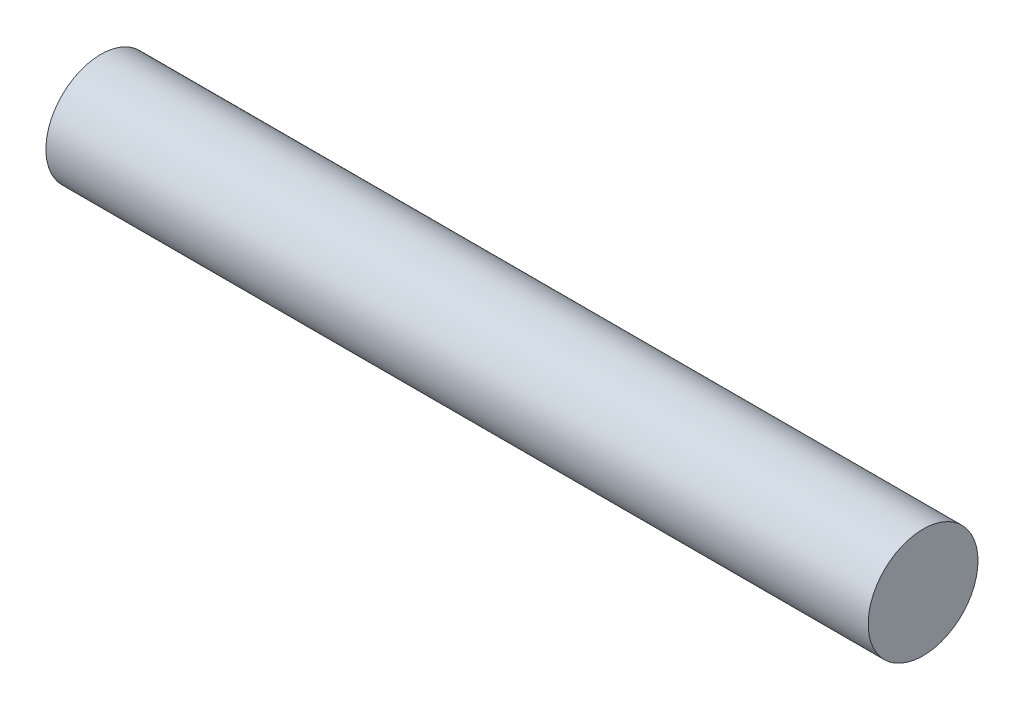
SolidWorks part; units mm, degrees
ref_plane "Front Plane" through (0, 0, 0) normal (0, 0, 1) x (1, 0, 0)
ref_plane "Top Plane" through (0, 0, 0) normal (0, 1, 0) x (1, 0, 0)
ref_plane "Right Plane" through (0, 0, 0) normal (1, 0, 0) x (0, 0, -1)
sketch "Sketch1" plane through (0, 0, 0) normal (0, 0, 1) x (1, 0, 0)
  line L0 (0, 0) -> (299.4969, 0)
  point P3 (0, 0)
sketch "Sketch2" plane through (0, 0, 0) normal (1, 0, 0) x (0, 0, -1)
  circle A0 centre (0, 0) radius 20
  dimension "D1" = 40
sweep "Sweep1" add path "Sketch1" circular profile diameter 40 parameters "D3"=40
